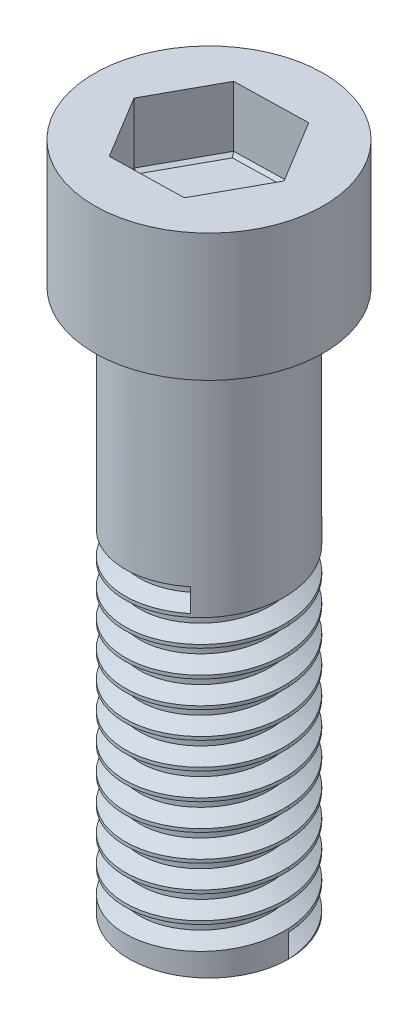
SolidWorks part; units mm, degrees
material "Malleable Cast Iron"
ref_plane "Front Plane" through (0, 0, 0) normal (0, 0, 1) x (1, 0, 0)
ref_plane "Top Plane" through (0, 0, 0) normal (0, 1, 0) x (1, 0, 0)
ref_plane "Right Plane" through (0, 0, 0) normal (1, 0, 0) x (0, 0, -1)
sketch "Sketch1" plane through (0, 0, 0) normal (0, 1, 0) x (1, 0, 0)
  circle A0 centre (0, 0) radius 3.175
extrude "Boss-Extrude1" add sketch "Sketch1" along normal blind 21.59
sketch "Sketch2" plane through (0, 21.59, 0) normal (0, 1, 0) x (1, 0, 0)
  circle A0 centre (0, 0) radius 4.5631
extrude "Boss-Extrude2" add sketch "Sketch2" along normal blind 5.08
sketch "Sketch3" plane through (0, 26.67, 0) normal (0, 1, 0) x (1, 0, 0)
  line L1 (-1.4054, -2.5637) -> (1.5176, -2.499)
  line L2 (1.5176, -2.499) -> (2.923, 0.0648)
  line L3 (2.923, 0.0648) -> (1.4054, 2.5637)
  line L4 (1.4054, 2.5637) -> (-1.5176, 2.499)
  line L5 (-1.5176, 2.499) -> (-2.923, -0.0648)
  line L6 (-2.923, -0.0648) -> (-1.4054, -2.5637)
  circle A0 centre (0, 0) radius 2.532 construction
extrude "Cut-Extrude1" cut sketch "Sketch3" against normal blind 2.54
chamfer "Chamfer1" distance 0.127 angle 45 6 edges at (-2.2203, 24.13, -1.2171) (-0.0561, 24.13, -2.5314) (2.1642, 24.13, -1.3143) (2.2203, 24.13, 1.2171) (0.0561, 24.13, 2.5314) (-2.1642, 24.13, 1.3143)
thread "Thread1" pitch 1.0583 method cut profile "Thread Profile1" start angle 0, offset 0, length 12.54, pitch 1.0583, diameter 6.35
ref_plane "Plane1" through (3.175, 0, 0) normal (0, 0, 1) x (1, 0, 0)
sketch "Thread Profile1" plane through (3.175, 0, 0) normal (0, 0, 1) x (1, 0, 0)
  line L0 (0, 0) -> (0, 1.0583) construction
  line L11 (0, 0) -> (0, 0.926)
  line L12 (0, 0.926) -> (-0.5728, 0.5953)
  line L13 (-0.5728, 0.5953) -> (-0.5728, 0.3307)
  line L15 (-0.5728, 0.3307) -> (0, 0)
  line L17 (-0.5728, 0.463) -> (0, 0.463) construction
  point P2 (0, 0)
  dimension "Pitch" = 1.0583
  dimension "Profile_Angle" = 60
  dimension "Profile_Land" = 0.2646
  dimension "Profile_Height" = 0.5728
